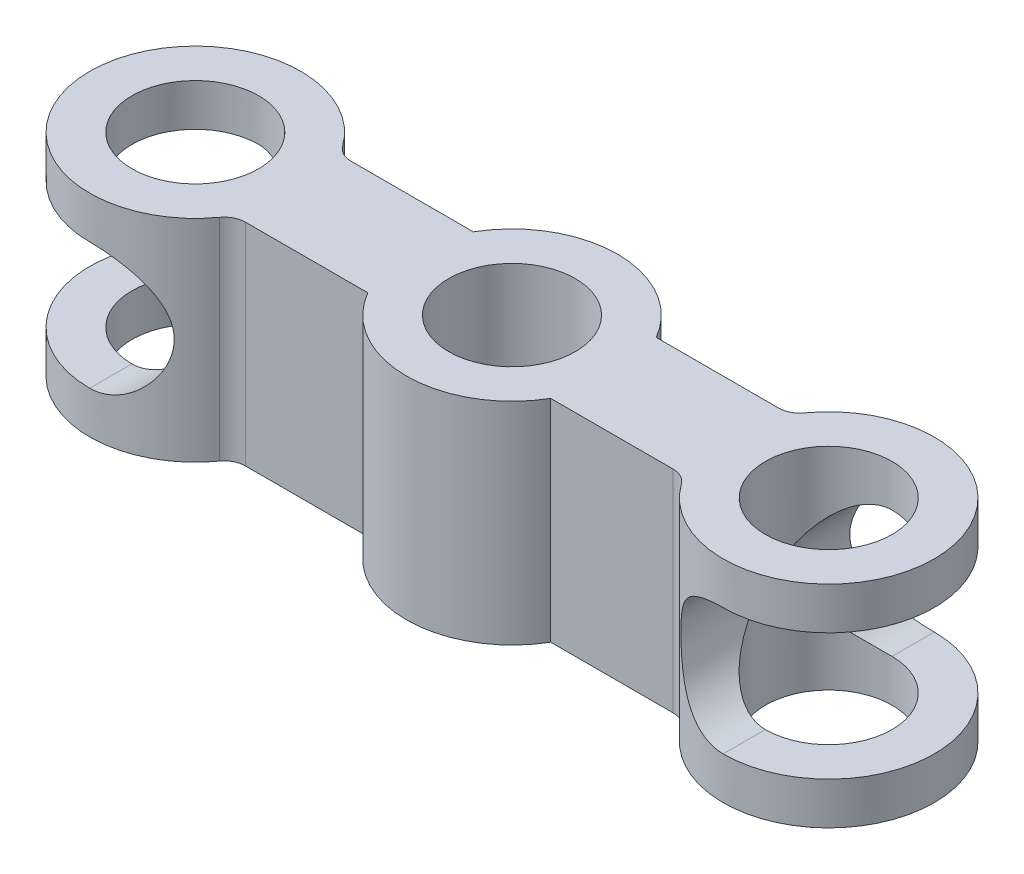
SolidWorks part; units mm, degrees
ref_plane "Front Plane" through (0, 0, 0) normal (0, 0, 1) x (1, 0, 0)
ref_plane "Top Plane" through (0, 0, 0) normal (0, 1, 0) x (1, 0, 0)
ref_plane "Right Plane" through (0, 0, 0) normal (1, 0, 0) x (0, 0, -1)
sketch "Sketch1" plane through (0, 0, 0) normal (0, 1, 0) x (1, 0, 0)
  line L1 (0, 2.5) -> (15, 2.5)
  line L2 (0, 2.5) -> (0, -2.5)
  line L3 (0, -2.5) -> (15, -2.5)
  line L4 (15, 2.5) -> (15, -2.5)
  dimension "D1" = 5
  dimension "D2" = 15
extrude "Boss-Extrude1" add sketch "Sketch1" along normal blind 10
sketch "Sketch2" plane through (0, 0, 0) normal (0, 1, 0) x (1, 0, 0)
  circle A0 centre (0, 0) radius 5
  dimension "D1" = 10
sketch "Sketch3" plane through (0, 0, 0) normal (0, 1, 0) x (1, 0, 0)
  circle A0 centre (0, 0) radius 3
  dimension "D1" = 6
extrude "Boss-Extrude2" add sketch "Sketch2" along normal up to surface (10 mm away) up to face at (7.5, 10, 0)
extrude "Cut-Extrude1" cut sketch "Sketch3" along normal up to next
sketch "Sketch4" plane through (0, 0, 0) normal (0, 0, 1) x (1, 0, 0)
  line L0 (0, 0) -> (0, 10) construction
  line L1 (3, 10) -> (-3, 10) construction
  line L2 (0, 8) -> (-5, 8)
  line L3 (-5, 10) -> (-5, 0) construction
  line L4 (0, 2) -> (-5, 2)
  line L5 (-5, 8) -> (-5, 2)
  arc A0 (0, 2) -> (0, 8) centre (0, 5) ccw
  dimension "D1" = 6
extrude "Cut-Extrude2" cut sketch "Sketch4" against normal through all both and the other way through all
fillet "Fillet1" radius 1 2 edges at (4.3301, 5, -2.5) (4.3301, 5, 2.5)
mirror "Mirror1" about plane through (15, 10, -2.5) normal (-1, 0, 0) of "Fillet1", "Cut-Extrude2", "Boss-Extrude2", "Cut-Extrude1", "Boss-Extrude1"
sketch "Sketch6" plane through (0, 0, 0) normal (0, 1, 0) x (1, 0, 0)
  circle A0 centre (15, 0) radius 5
  dimension "D1" = 10
  dimension "D2" = 0
  dimension "D3" = 15
extrude "Boss-Extrude3" add sketch "Sketch6" along normal up to surface (10 mm away) up to face at (30, 10, 3)
sketch "Sketch7" plane through (0, 0, 0) normal (0, 1, 0) x (1, 0, 0)
  circle A0 centre (15, 0) radius 3
  arc A1 (19.3301, 2.5) -> (10.6699, 2.5) centre (15, 0) ccw construction
  dimension "D1" = 6
extrude "Cut-Extrude3" cut sketch "Sketch7" along normal up to surface (10 mm away) up to face at (30, 10, 3)
